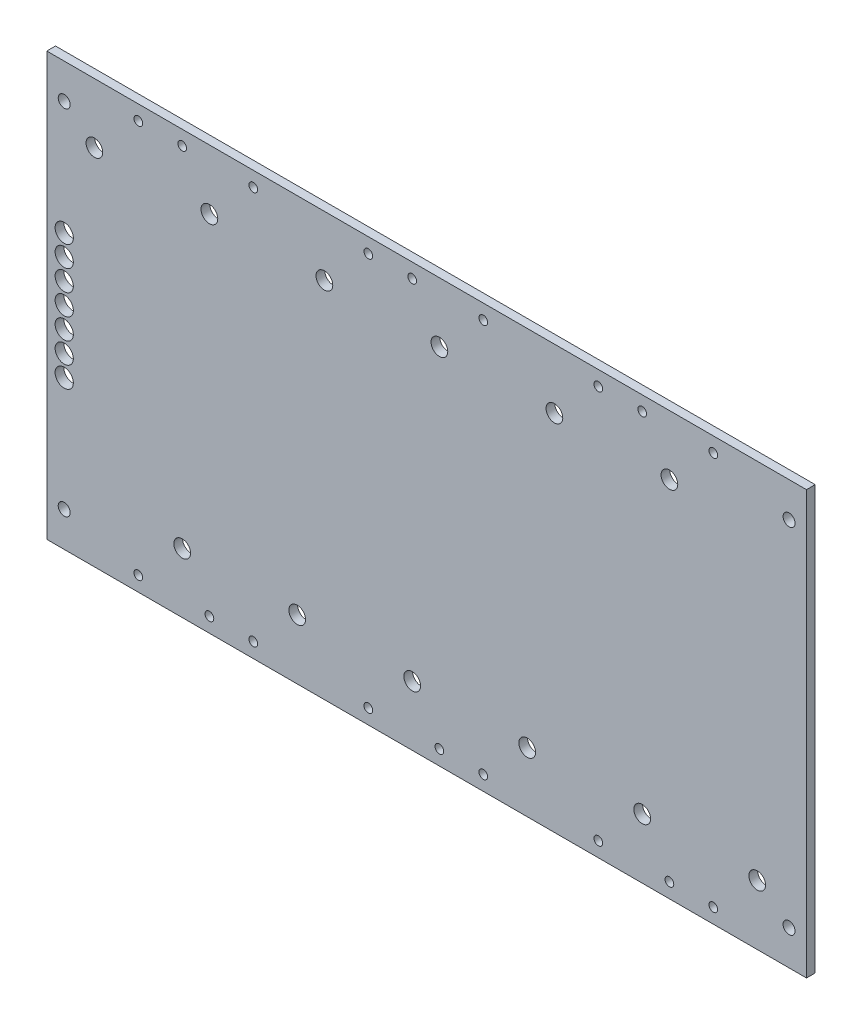
SolidWorks part; units mm, degrees
ref_plane "Front Plane" through (0, 0, 0) normal (0, 0, 1) x (1, 0, 0)
ref_plane "Top Plane" through (0, 0, 0) normal (0, 1, 0) x (1, 0, 0)
ref_plane "Right Plane" through (0, 0, 0) normal (1, 0, 0) x (0, 0, -1)
sketch "Sketch1" plane through (0, 0, 0) normal (0, 0, 1) x (1, 0, 0)
  line L0 (20.955, 77.0636) -> (20.955, 0) construction
  line L1 (0, 0) -> (132.08, 0)
  line L2 (0, 0) -> (0, 77.0636) construction
  line L3 (0, 77.0636) -> (132.08, 77.0636)
  line L4 (132.08, 77.0636) -> (132.08, 0)
  line L5 (20.6502, 77.0636) -> (20.6502, 0) construction
  line L6 (10.3251, 74.3712) -> (0, 74.3712) construction
  line L7 (10.3251, 74.3712) -> (20.6502, 74.3712) construction
  line L8 (10.3251, 2.6924) -> (10.3251, 0) construction
  line L9 (10.3251, 74.3712) -> (10.3251, 77.0636) construction
  line L10 (18.3261, 66.1543) -> (20.6502, 66.1543) construction
  line L11 (2.3241, 66.1543) -> (0, 66.1543) construction
  line L12 (18.3261, 10.9093) -> (20.6502, 10.9093) construction
  line L13 (41.6052, 77.0636) -> (41.6052, 0) construction
  line L14 (18.3261, 66.1543) -> (18.3261, 77.0636) construction
  line L15 (18.3261, 10.9093) -> (18.3261, 0) construction
  line L16 (20.955, 66.1543) -> (23.2791, 66.1543) construction
  line L17 (41.6052, 66.1543) -> (36.2579, 66.1543) construction
  line L18 (41.6052, 74.3712) -> (20.955, 74.3712) construction
  line L19 (31.2801, 74.3712) -> (31.2801, 77.0636) construction
  line L20 (31.2801, 0) -> (31.2801, 2.6924) construction
  line L21 (0, 77.0636) -> (-6.35, 77.0636)
  line L22 (-6.35, 77.0636) -> (-6.35, 0)
  line L23 (-6.35, 0) -> (0, 0)
  line L24 (41.6052, 10.9093) -> (39.2811, 10.9093) construction
  line L25 (41.6052, 2.6924) -> (31.2801, 2.6924) construction
  line L26 (83.5152, 77.0636) -> (83.5152, 0) construction
  line L27 (-3.175, 70.7136) -> (-3.175, 77.0636) construction
  line L28 (-3.175, 6.35) -> (-3.175, 0) construction
  line L29 (62.865, 77.0636) -> (62.865, 0) construction
  line L30 (62.5602, 77.0636) -> (62.5602, 0) construction
  line L31 (41.91, 0) -> (41.91, 77.0636) construction
  line L32 (125.4252, 77.0636) -> (125.4252, 0) construction
  line L33 (104.775, 77.0636) -> (104.775, 0) construction
  line L34 (104.4702, 77.0636) -> (104.4702, 0) construction
  line L35 (83.82, 0) -> (83.82, 77.0636) construction
  line L36 (41.6052, 77.0636) -> (83.5152, 77.0636) construction
  line L37 (128.905, 77.0636) -> (128.905, 70.7136) construction
  line L38 (128.905, 0) -> (128.905, 6.35) construction
  line L39 (20.955, 2.6924) -> (23.2791, 2.6924) construction
  line L40 (23.2791, 2.6924) -> (65.1891, 2.6924) construction
  line L41 (94.1451, 74.3712) -> (115.1001, 74.3712) construction
  line L42 (-3.175, 38.5318) -> (-6.35, 38.5318) construction
  line L43 (-3.175, 38.5318) -> (-3.175, 42.3418) construction
  circle A0 centre (10.3251, 74.3712) radius 0.7937
  circle A1 centre (10.3251, 2.6924) radius 0.7937
  circle A2 centre (2.3241, 66.1543) radius 1.524
  circle A3 centre (18.3261, 74.4347) radius 0.7937
  circle A4 centre (18.3261, 10.9093) radius 1.524
  circle A5 centre (23.2791, 66.1543) radius 1.524
  circle A6 centre (31.2801, 74.3712) radius 0.7937
  circle A7 centre (31.2801, 2.6924) radius 0.7937
  circle A8 centre (39.2811, 10.9093) radius 1.524
  circle A9 centre (31.2801, 2.6924) radius 0.7937
  circle A10 centre (65.1891, 66.1543) radius 1.524
  circle A11 centre (73.1901, 2.6924) radius 0.7937
  circle A12 centre (73.1901, 2.6924) radius 0.7937
  circle A13 centre (81.1911, 10.9093) radius 1.524
  circle A14 centre (73.1901, 74.3712) radius 0.7937
  circle A15 centre (65.1891, 2.6924) radius 0.7937
  circle A16 centre (52.2351, 74.3712) radius 0.7937
  circle A17 centre (44.2341, 66.1543) radius 1.524
  circle A18 centre (-3.175, 70.7136) radius 1.0922
  circle A19 centre (-3.175, 6.35) radius 1.0922
  circle A20 centre (60.2361, 10.9093) radius 1.524
  circle A21 centre (52.2351, 2.6924) radius 0.7937
  circle A22 centre (107.0991, 66.1543) radius 1.524
  circle A23 centre (115.1001, 2.6924) radius 0.7937
  circle A24 centre (115.1001, 2.6924) radius 0.7937
  circle A25 centre (123.1011, 10.9093) radius 1.524
  circle A26 centre (60.2361, 74.4347) radius 0.7937
  circle A27 centre (102.1461, 74.4347) radius 0.7937
  circle A28 centre (94.1451, 74.3712) radius 0.7937
  circle A29 centre (86.1441, 66.1543) radius 1.524
  circle A30 centre (102.1461, 10.9093) radius 1.524
  circle A31 centre (94.1451, 2.6924) radius 0.7937
  circle A32 centre (128.905, 70.7136) radius 1.0922
  circle A33 centre (128.905, 6.35) radius 1.0922
  circle A34 centre (23.2791, 2.6924) radius 0.7937
  circle A35 centre (60.2361, 74.4347) radius 0.7937 [skipped]
  circle A36 centre (115.1001, 74.3712) radius 0.7937 [skipped]
  circle A37 centre (107.0991, 2.6924) radius 0.7937
  circle A38 centre (102.1461, 74.4347) radius 0.7937
  circle A39 centre (115.1001, 74.3712) radius 0.7937
  circle A40 centre (-3.175, 38.5318) radius 1.6593
  circle A41 centre (-3.175, 42.3418) radius 1.6593
  circle A42 centre (-3.175, 46.1518) radius 1.6593
  circle A43 centre (-3.175, 49.9618) radius 1.6593
  circle A44 centre (-3.175, 38.5318) radius 1.6593
  circle A45 centre (-3.175, 42.3418) radius 1.6593
  circle A46 centre (-3.175, 46.1518) radius 1.6593
  circle A47 centre (-3.175, 34.7218) radius 1.6593
  circle A48 centre (-3.175, 38.5318) radius 1.6593
  circle A49 centre (-3.175, 42.3418) radius 1.6593
  circle A50 centre (-3.175, 30.9118) radius 1.6593
  circle A51 centre (-3.175, 34.7218) radius 1.6593
  circle A52 centre (-3.175, 38.5318) radius 1.6593
  circle A53 centre (-3.175, 34.7218) radius 1.6593
  circle A54 centre (-3.175, 30.9118) radius 1.6593
  circle A55 centre (-3.175, 27.1018) radius 1.6593
  dimension "D6" = 1.5875
  dimension "D7" = 3.048
  dimension "D13" = 2.1844
  dimension "D15" = 20.6502
  dimension "D11" = 1.5875
  dimension "D16" = 3
  dimension "D18" = 41.91
  dimension "D24" = 3.3186
  dimension "D1" = 77.0636
  dimension "D2" = 132.08
  dimension "D3" = 20.6502
  dimension "D4" = 20.955
  dimension "D5" = 71.6788
  dimension "D8" = 16.002
  dimension "D9" = 55.245
  dimension "D10" = 8.2804
  dimension "D12" = 6.35
  dimension "D14" = 6.35
  dimension "D17" = 3
  dimension "D19" = 71.6788
  dimension "D20" = 3.175
  dimension "D21" = 41.91
  dimension "D23" = 20.955
  dimension "D27" = 3.81
  dimension "D22" = 2
  dimension "D25" = 4
  dimension "D26" = 4
extrude "Boss-Extrude1" add sketch "Sketch1" along normal blind 1.5875 contours L1 L4 L3 L2 A4 A2 A1 A0 | L22 L23 L2 L21 A19 A18 | L4 region at (63.2487, 38.5318, 0)
